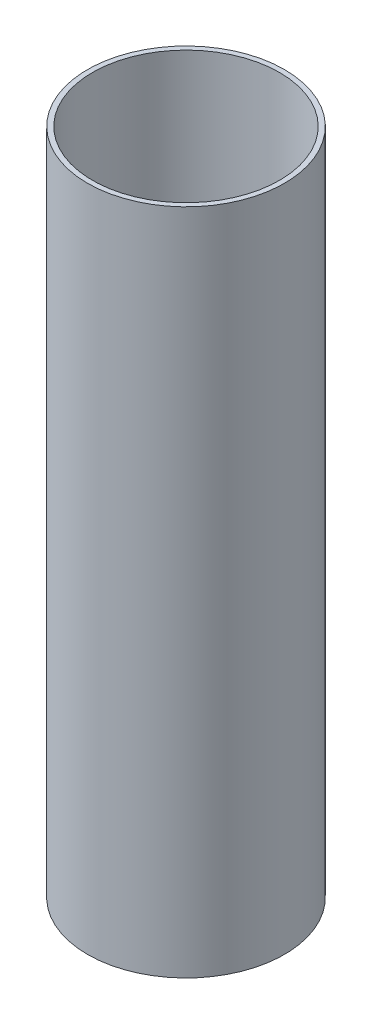
SolidWorks part; units mm, degrees
material "PVC Rigid"
ref_plane "Front Plane" through (0, 0, 0) normal (0, 0, 1) x (1, 0, 0)
ref_plane "Top Plane" through (0, 0, 0) normal (0, 1, 0) x (1, 0, 0)
ref_plane "Right Plane" through (0, 0, 0) normal (1, 0, 0) x (0, 0, -1)
sketch "Sketch1" plane through (0, 0, 0) normal (0, 1, 0) x (1, 0, 0)
  circle A0 centre (0, 0) radius 93.6625
  circle A1 centre (0, 0) radius 88.9
  dimension "D1" = 187.325
  dimension "D2" = 177.8
extrude "Boss-Extrude1" add sketch "Sketch1" along normal mid plane 635
